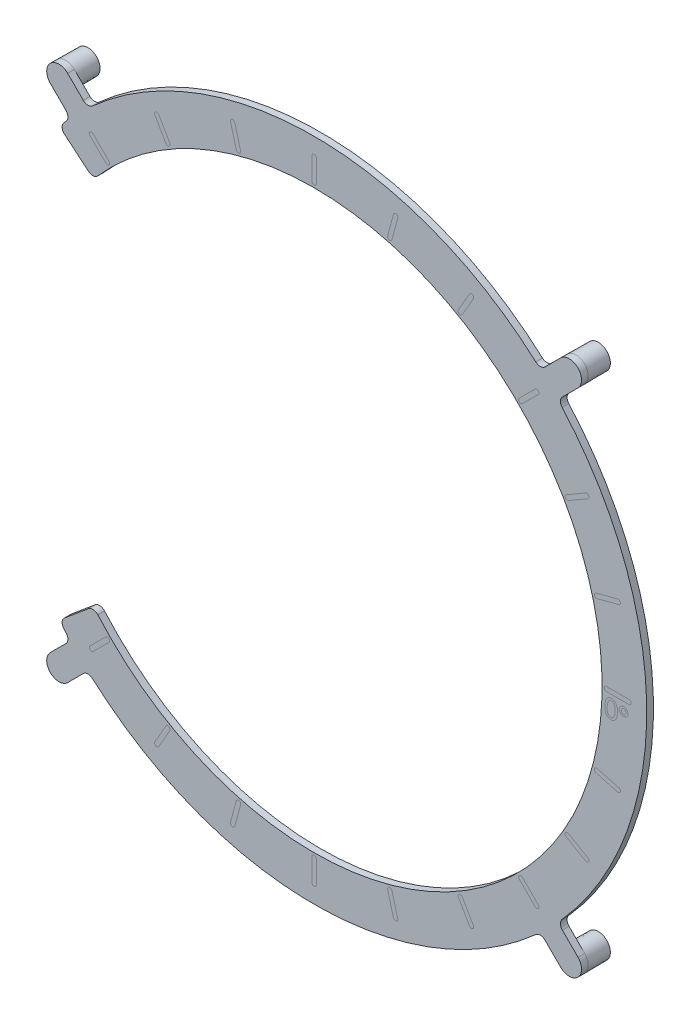
SolidWorks part; units mm, degrees
material "ABS"
ref_plane "Front Plane" through (0, 0, 0) normal (0, 0, 1) x (1, 0, 0)
ref_plane "Top Plane" through (0, 0, 0) normal (0, 1, 0) x (1, 0, 0)
ref_plane "Right Plane" through (0, 0, 0) normal (1, 0, 0) x (0, 0, -1)
sketch "main_features_sketch" plane through (0, 0, 0) normal (0, 0, 1) x (1, 0, 0)
  line L0 (0, 0) -> (149, 0) construction
  line L9 (-98.8197, -82.9196) -> (-114.1406, -95.7754)
  line L24 (-98.8197, 82.9196) -> (-114.1406, 95.7754)
  line L25 (0, 0) -> (-98.8197, 82.9196) construction
  line L26 (118.1891, -110.4109) -> (109.1762, -101.398)
  line L27 (110.4109, -118.1891) -> (101.398, -109.1762)
  line L28 (-110.4109, -118.1891) -> (-101.398, -109.1762)
  line L29 (-118.1891, -110.4109) -> (-109.1762, -101.398)
  line L30 (-118.1891, 110.4109) -> (-109.1762, 101.398)
  line L31 (-110.4109, 118.1891) -> (-101.398, 109.1762)
  line L32 (110.4109, 118.1891) -> (101.398, 109.1762)
  line L33 (118.1891, 110.4109) -> (109.1762, 101.398)
  circle A0 centre (114.3, -114.3) radius 5.5
  circle A1 centre (114.3, 114.3) radius 5.5
  arc A2 (-98.8197, -82.9196) -> (-98.8197, 82.9196) centre (0, 0) ccw
  arc A3 (-114.1406, -95.7754) -> (-114.1406, 95.7754) centre (0, 0) ccw
  circle A4 centre (0, 0) radius 127 construction
  circle A5 centre (-114.3, -114.3) radius 5.5
  circle A6 centre (-114.3, 114.3) radius 5.5
  point P29 (0, 0)
  point P46 (0, 0)
  dimension "D1" = 20
  dimension "D2" = 2
  dimension "D3" = 11
  dimension "D7" = 4
  dimension "D8" = 140
extrude "ring" add sketch "main_features_sketch" along normal blind 3 contours A3 L24 A2 L9 | A5 L28 A3 L29 | A5 | A6 | A6 L30 A3 L31 | A1 | A3 L33 A1 L32 | A3 L27 A0 L26 | A0 A2 region at (132.9755, 0, 0) region at (-108.3539, -108.3539, 0) region at (-114.3, -114.3, 0) region at (-108.3539, 108.3539, 0) region at (108.3539, -108.3539, 0) region at (-114.3, 114.3, 0) region at (114.3, -114.3, 0) region at (108.3539, 108.3539, 0) region at (114.3, 114.3, 0)
extrude "pegs" add sketch "main_features_sketch<3>" against normal blind 10 draft 0.5 contours A6 | A5 | A0 | A1 region at (-114.3, -114.3, 0) region at (-114.3, 114.3, 0) region at (114.3, -114.3, 0) region at (114.3, 114.3, 0)
sketch "main_features_sketch<3>" plane through (0, 0, 0) normal (0, 0, 1) x (1, 0, 0) same geometry as "main_features_sketch"
fillet "Fillet1" radius 3 12 edges at (-98.8197, -82.9196, 1.5) (-114.1406, -95.7754, 1.5) (-109.1762, -101.398, 1.5) (-101.398, -109.1762, 1.5) (101.398, -109.1762, 1.5) (109.1762, -101.398, 1.5) (109.1762, 101.398, 1.5) (101.398, 109.1762, 1.5) (-98.8197, 82.9196, 1.5) (-114.1406, 95.7754, 1.5) (-101.398, 109.1762, 1.5) (-109.1762, 101.398, 1.5)
sketch "tick_marks" plane through (0, 0, 3) normal (0, 0, 1) x (1, 0, 0)
  line L0 (-92.631, 92.631) -> (-99.7021, 99.7021) construction
  line L1 (-93.3381, 91.9239) -> (-100.4092, 98.9949)
  line L2 (-91.9239, 93.3381) -> (-98.9949, 100.4092)
  line L3 (-65.5, 113.4493) -> (-70.5, 122.1096) construction
  line L4 (-66.366, 112.9493) -> (-71.366, 121.6096)
  line L5 (-64.634, 113.9493) -> (-69.634, 122.6096)
  line L6 (-33.9053, 126.5363) -> (-36.4935, 136.1955) construction
  line L7 (-34.8712, 126.2775) -> (-37.4594, 135.9367)
  line L8 (-32.9394, 126.7951) -> (-35.5276, 136.4544)
  line L9 (0, 131) -> (0, 141) construction
  line L10 (-1, 131) -> (-1, 141)
  line L11 (1, 131) -> (1, 141)
  line L12 (33.9053, 126.5363) -> (36.4935, 136.1955) construction
  line L13 (32.9394, 126.7951) -> (35.5276, 136.4544)
  line L14 (34.8712, 126.2775) -> (37.4594, 135.9367)
  line L15 (65.5, 113.4493) -> (70.5, 122.1096) construction
  line L16 (64.634, 113.9493) -> (69.634, 122.6096)
  line L17 (66.366, 112.9493) -> (71.366, 121.6096)
  line L18 (92.631, 92.631) -> (99.7021, 99.7021) construction
  line L19 (91.9239, 93.3381) -> (98.9949, 100.4092)
  line L20 (93.3381, 91.9239) -> (100.4092, 98.9949)
  line L21 (113.4493, 65.5) -> (122.1096, 70.5) construction
  line L22 (112.9493, 66.366) -> (121.6096, 71.366)
  line L23 (113.9493, 64.634) -> (122.6096, 69.634)
  line L24 (126.5363, 33.9053) -> (136.1955, 36.4935) construction
  line L25 (126.2775, 34.8712) -> (135.9367, 37.4594)
  line L26 (126.7951, 32.9394) -> (136.4544, 35.5276)
  line L27 (131, 0) -> (141, 0) construction
  line L28 (131, 1) -> (141, 1)
  line L29 (131, -1) -> (141, -1)
  line L30 (0, 0) -> (-92.631, 92.631) construction
  line L31 (0, 0) -> (-65.5, 113.4493) construction
  line L32 (0, 0) -> (-96.1665, -96.1665) construction
  line L33 (126.5363, -33.9053) -> (136.1955, -36.4935) construction
  line L34 (126.7951, -32.9394) -> (136.4544, -35.5276)
  line L35 (126.2775, -34.8712) -> (135.9367, -37.4594)
  line L36 (113.4493, -65.5) -> (122.1096, -70.5) construction
  line L37 (113.9493, -64.634) -> (122.6096, -69.634)
  line L38 (112.9493, -66.366) -> (121.6096, -71.366)
  line L39 (92.631, -92.631) -> (99.7021, -99.7021) construction
  line L40 (93.3381, -91.9239) -> (100.4092, -98.9949)
  line L41 (91.9239, -93.3381) -> (98.9949, -100.4092)
  line L42 (65.5, -113.4493) -> (70.5, -122.1096) construction
  line L43 (66.366, -112.9493) -> (71.366, -121.6096)
  line L44 (64.634, -113.9493) -> (69.634, -122.6096)
  line L45 (33.9053, -126.5363) -> (36.4935, -136.1955) construction
  line L46 (34.8712, -126.2775) -> (37.4594, -135.9367)
  line L47 (32.9394, -126.7951) -> (35.5276, -136.4544)
  line L48 (0, -131) -> (0, -141) construction
  line L49 (1, -131) -> (1, -141)
  line L50 (-1, -131) -> (-1, -141)
  line L51 (-33.9053, -126.5363) -> (-36.4935, -136.1955) construction
  line L52 (-32.9394, -126.7951) -> (-35.5276, -136.4544)
  line L53 (-34.8712, -126.2775) -> (-37.4594, -135.9367)
  line L54 (-65.5, -113.4493) -> (-70.5, -122.1096) construction
  line L55 (-64.634, -113.9493) -> (-69.634, -122.6096)
  line L56 (-66.366, -112.9493) -> (-71.366, -121.6096)
  line L57 (-92.631, -92.631) -> (-99.7021, -99.7021) construction
  line L58 (-91.9239, -93.3381) -> (-98.9949, -100.4092)
  line L59 (-93.3381, -91.9239) -> (-100.4092, -98.9949)
  arc A0 (-96.1665, 96.1665) -> (-96.1665, -96.1665) centre (0, 0) cw construction
  arc A1 (-93.3381, 91.9239) -> (-91.9239, 93.3381) centre (-92.631, 92.631) ccw
  arc A2 (-98.9949, 100.4092) -> (-100.4092, 98.9949) centre (-99.7021, 99.7021) ccw
  arc A3 (-66.366, 112.9493) -> (-64.634, 113.9493) centre (-65.5, 113.4493) ccw
  arc A4 (-69.634, 122.6096) -> (-71.366, 121.6096) centre (-70.5, 122.1096) ccw
  arc A5 (-34.8712, 126.2775) -> (-32.9394, 126.7951) centre (-33.9053, 126.5363) ccw
  arc A6 (-35.5276, 136.4544) -> (-37.4594, 135.9367) centre (-36.4935, 136.1955) ccw
  arc A7 (-1, 131) -> (1, 131) centre (0, 131) ccw
  arc A8 (1, 141) -> (-1, 141) centre (0, 141) ccw
  arc A9 (32.9394, 126.7951) -> (34.8712, 126.2775) centre (33.9053, 126.5363) ccw
  arc A10 (37.4594, 135.9367) -> (35.5276, 136.4544) centre (36.4935, 136.1955) ccw
  arc A11 (64.634, 113.9493) -> (66.366, 112.9493) centre (65.5, 113.4493) ccw
  arc A12 (71.366, 121.6096) -> (69.634, 122.6096) centre (70.5, 122.1096) ccw
  arc A13 (91.9239, 93.3381) -> (93.3381, 91.9239) centre (92.631, 92.631) ccw
  arc A14 (100.4092, 98.9949) -> (98.9949, 100.4092) centre (99.7021, 99.7021) ccw
  arc A15 (112.9493, 66.366) -> (113.9493, 64.634) centre (113.4493, 65.5) ccw
  arc A16 (122.6096, 69.634) -> (121.6096, 71.366) centre (122.1096, 70.5) ccw
  arc A17 (126.2775, 34.8712) -> (126.7951, 32.9394) centre (126.5363, 33.9053) ccw
  arc A18 (136.4544, 35.5276) -> (135.9367, 37.4594) centre (136.1955, 36.4935) ccw
  arc A19 (131, 1) -> (131, -1) centre (131, 0) ccw
  arc A20 (141, -1) -> (141, 1) centre (141, 0) ccw
  arc A21 (126.7951, -32.9394) -> (126.2775, -34.8712) centre (126.5363, -33.9053) ccw
  arc A22 (135.9367, -37.4594) -> (136.4544, -35.5276) centre (136.1955, -36.4935) ccw
  arc A23 (113.9493, -64.634) -> (112.9493, -66.366) centre (113.4493, -65.5) ccw
  arc A24 (121.6096, -71.366) -> (122.6096, -69.634) centre (122.1096, -70.5) ccw
  arc A25 (93.3381, -91.9239) -> (91.9239, -93.3381) centre (92.631, -92.631) ccw
  arc A26 (98.9949, -100.4092) -> (100.4092, -98.9949) centre (99.7021, -99.7021) ccw
  arc A27 (66.366, -112.9493) -> (64.634, -113.9493) centre (65.5, -113.4493) ccw
  arc A28 (69.634, -122.6096) -> (71.366, -121.6096) centre (70.5, -122.1096) ccw
  arc A29 (34.8712, -126.2775) -> (32.9394, -126.7951) centre (33.9053, -126.5363) ccw
  arc A30 (35.5276, -136.4544) -> (37.4594, -135.9367) centre (36.4935, -136.1955) ccw
  arc A31 (1, -131) -> (-1, -131) centre (0, -131) ccw
  arc A32 (-1, -141) -> (1, -141) centre (0, -141) ccw
  arc A33 (-32.9394, -126.7951) -> (-34.8712, -126.2775) centre (-33.9053, -126.5363) ccw
  arc A34 (-37.4594, -135.9367) -> (-35.5276, -136.4544) centre (-36.4935, -136.1955) ccw
  arc A35 (-64.634, -113.9493) -> (-66.366, -112.9493) centre (-65.5, -113.4493) ccw
  arc A36 (-71.366, -121.6096) -> (-69.634, -122.6096) centre (-70.5, -122.1096) ccw
  arc A37 (-91.9239, -93.3381) -> (-93.3381, -91.9239) centre (-92.631, -92.631) ccw
  arc A38 (-100.4092, -98.9949) -> (-98.9949, -100.4092) centre (-99.7021, -99.7021) ccw
  point P6 (-96.1665, 96.1665)
  point P11 (-91.9648, -103.7421)
  point P12 (0, 0)
  point P15 (-68, 117.7795)
  point P22 (-35.1994, 131.3659)
  point P29 (0, 136)
  point P36 (35.1994, 131.3659)
  point P43 (68, 117.7795)
  point P50 (96.1665, 96.1665)
  point P57 (117.7795, 68)
  point P64 (131.3659, 35.1994)
  point P71 (136, 0)
  point P80 (131.3659, -35.1994)
  point P87 (117.7795, -68)
  point P94 (96.1665, -96.1665)
  point P101 (68, -117.7795)
  point P108 (35.1994, -131.3659)
  point P115 (0, -136)
  point P122 (-35.1994, -131.3659)
  point P129 (-68, -117.7795)
  point P136 (-96.1665, -96.1665)
  dimension "D1" = 2
  dimension "D2" = 10
  dimension "D4" = 15
  dimension "D5" = 90
  dimension "D6" = 136
  dimension "D3" = 19
extrude "cut_ticks" cut sketch "tick_marks" against normal blind 1
extrude "extrude_ticks" add sketch "tick_marks<3>" against normal blind 1 separate body
sketch "tick_marks<3>" plane through (0, 0, 3) normal (0, 0, 1) x (1, 0, 0) same geometry as "tick_marks"
sketch "numbers_sketch" plane through (0, 0, 3) normal (0, 0, 1) x (1, 0, 0)
  line L0 (-91.966, 108.1954) -> (-84.1943, 99.0521) construction
  line L1 (-60.8293, 128.3113) -> (-55.6888, 117.4681) construction
  line L2 (-25.5472, 139.683) -> (-23.3883, 127.8788) construction
  line L3 (11.4759, 141.5355) -> (10.5061, 129.5748) construction
  line L4 (47.717, 133.7426) -> (43.6845, 122.4404) construction
  line L5 (80.7062, 116.8354) -> (73.8859, 106.962) construction
  line L6 (108.1954, 91.966) -> (99.0521, 84.1943) construction
  line L7 (128.3113, 60.8293) -> (117.4681, 55.6888) construction
  line L8 (139.683, 25.5472) -> (127.8788, 23.3883) construction
  line L9 (141.5355, -11.4759) -> (129.5748, -10.5061) construction
  line L10 (133.7426, -47.717) -> (122.4404, -43.6845) construction
  line L11 (116.8354, -80.7062) -> (106.962, -73.8859) construction
  line L12 (91.966, -108.1954) -> (84.1943, -99.0521) construction
  line L13 (60.8293, -128.3113) -> (55.6888, -117.4681) construction
  line L14 (25.5472, -139.683) -> (23.3883, -127.8788) construction
  line L15 (-11.4759, -141.5355) -> (-10.5061, -129.5748) construction
  line L16 (-47.717, -133.7426) -> (-43.6845, -122.4404) construction
  line L17 (-80.7062, -116.8354) -> (-73.8859, -106.962) construction
  line L18 (-108.1954, -91.966) -> (-99.0521, -84.1943) construction
  line L19 (0, 0) -> (-84.1943, 99.0521) construction
  line L20 (0, 0) -> (-55.6888, 117.4681) construction
  arc A3 (-96.1665, -96.1665) -> (-96.1665, 96.1665) centre (0, 0) ccw construction
  text T0 "<b>0°</b>" font "Century Gothic" height 8
  point P1 (0, 0)
  point P7 (-88.0802, 103.6238)
  dimension "D2" = 15
  dimension "D3" = 12
  dimension "D4" = 11
  dimension "D1" = 19
extrude "cut_numbers" cut sketch "numbers_sketch" against normal blind 1
extrude "extrude_numbers" add sketch "numbers_sketch<2>" against normal blind 1 separate body
sketch "numbers_sketch<2>" plane through (0, 0, 3) normal (0, 0, 1) x (1, 0, 0) same geometry as "numbers_sketch"
